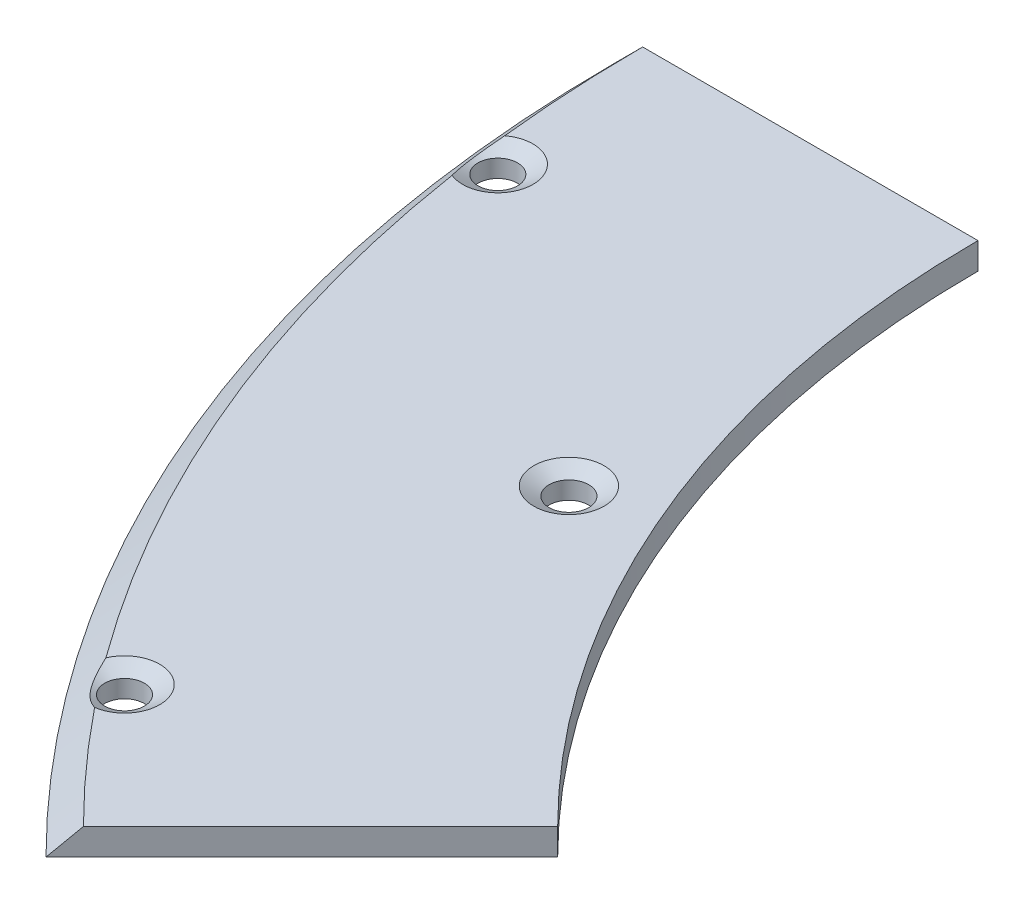
SolidWorks part; units mm, degrees
ref_plane "Front Plane" through (0, 0, 0) normal (0, 0, 1) x (1, 0, 0)
ref_plane "Top Plane" through (0, 0, 0) normal (0, 1, 0) x (1, 0, 0)
ref_plane "Right Plane" through (0, 0, 0) normal (1, 0, 0) x (0, 0, -1)
sketch "Sketch1" plane through (0, 0, 0) normal (0, 1, 0) x (1, 0, 0)
  line L0 (0, 0) -> (-115, 0) construction
  line L1 (-81.3173, -81.3173) -> (0, 0) construction
  line L2 (-115, 0) -> (-156, 0)
  line L3 (-110.3087, -110.3087) -> (-81.3173, -81.3173)
  line L4 (-119.7964, -91.923) -> (-91.2356, -70.0076) construction
  line L5 (-91.2356, -70.0076) -> (0, 0) construction
  line L6 (0, 0) -> (-114.0162, -15.0105) construction
  line L7 (-114.0162, -15.0105) -> (-149.7082, -19.7095) construction
  line L8 (-149.7082, -19.7095) -> (-106.2461, -44.0086) construction
  line L9 (-106.2461, -44.0086) -> (-119.7964, -91.923) construction
  arc A0 (-115, 0) -> (-81.3173, -81.3173) centre (0, 0) ccw
  arc A1 (-156, 0) -> (-110.3087, -110.3087) centre (0, 0) ccw
  circle A2 centre (-149.7082, -19.7095) radius 2.25
  circle A3 centre (-119.7964, -91.923) radius 2.25
  dimension "D2" = 115
  dimension "D3" = 156
  dimension "D5" = 4.5
  dimension "D6" = 151
  dimension "D1" = 45
  dimension "D4" = 30
extrude "Boss-Extrude1" add sketch "Sketch1" along normal blind 3
chamfer "Chamfer2" distance 1 angle 60 2 edges at (-119.7964, 3, 94.173) (-149.7082, 3, 21.9595) first distance on face at (-119.7964, 3, 94.173) first distance on face at (-149.7082, 3, 21.9595)
sketch "Sketch2" plane through (0, 3, 0) normal (0, 1, 0) x (1, 0, 0)
  line L0 (-114.0991, -47.2614) -> (-115, 0) construction
  line L1 (-114.0991, -47.2614) -> (0, 0) construction
  line L2 (-114.0991, -47.2614) -> (-81.3173, -81.3173) construction
  circle A0 centre (-114.0991, -47.2614) radius 2.25
  circle A1 centre (-149.7082, -19.7095) radius 2.25 construction
  dimension "D1" = 123.5
extrude "Cut-Extrude1" cut sketch "Sketch2" against normal through all
chamfer "Chamfer1" distance 3 angle 45 1 edges at (-144.1252, 3, 59.6986)
chamfer "Chamfer3" distance 1 angle 60 1 edges at (-114.0991, 3, 49.5114) first distance on face at (-114.0991, 0, 49.5114)
